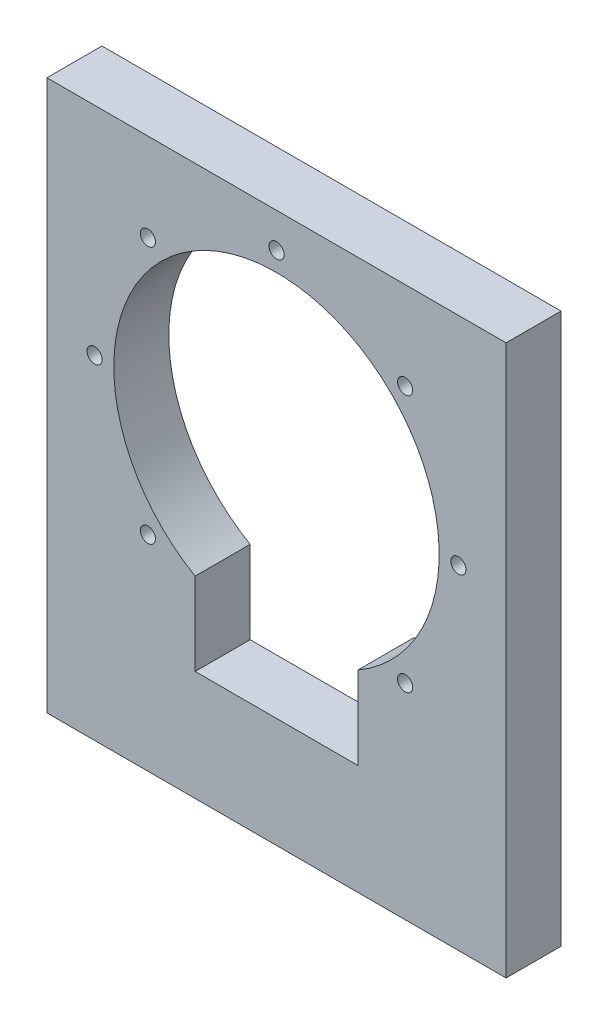
SolidWorks part; units mm, degrees
material "1060 Alloy"
ref_plane "Front Plane" through (0, 0, 0) normal (0, 0, 1) x (1, 0, 0)
ref_plane "Top Plane" through (0, 0, 0) normal (0, 1, 0) x (1, 0, 0)
ref_plane "Right Plane" through (0, 0, 0) normal (1, 0, 0) x (0, 0, -1)
sketch "Sketch1" plane through (0, 0, 0) normal (0, 0, 1) x (1, 0, 0)
  line L1 (0, 76.2) -> (106, 76.2)
  line L5 (0, 76.2) -> (0, -50.8)
  line L6 (0, -50.8) -> (106, -50.8)
  line L7 (0, 76.2) -> (0, -50.8) construction
  line L8 (53, 26.2) -> (53, -11.3) construction
  line L9 (53, 26.2) -> (34.2182, -6.3309) construction
  line L10 (53, 26.2) -> (71.7818, -6.3309) construction
  line L11 (34.2182, -6.3309) -> (34.2182, -25.4)
  line L12 (71.7818, -6.3309) -> (71.7818, -25.4)
  line L13 (71.7818, -25.4) -> (34.2182, -25.4)
  line L21 (106, 76.2) -> (106, -50.8)
  arc A6 (71.7818, -6.3309) -> (34.2182, -6.3309) centre (53, 26.2) ccw
  circle A7 centre (53, 26.2) radius 42 construction
  circle A9 centre (82.6985, 55.8985) radius 1.746
  circle A10 centre (95, 26.2) radius 1.746
  circle A11 centre (82.6985, -3.4985) radius 1.746
  circle A13 centre (23.3015, -3.4985) radius 1.746
  circle A14 centre (11, 26.2) radius 1.746
  circle A15 centre (23.3015, 55.8985) radius 1.746
  circle A33 centre (53, 68.2) radius 1.746
  point P0 (0, 0)
  point P6 (53, 26.2)
  point P32 (53, 26.2)
  point P38 (53, 26.2)
  dimension "D6" = 75.127
  dimension "D7" = 84
  dimension "D8" = 3.492
  dimension "D3" = 3.492
  dimension "D9" = 3.492
  dimension "D4" = 53
  dimension "D5" = 50
  dimension "D10" = 30
  dimension "D11" = 30
  dimension "D2" = 25.4
  dimension "D12" = 127
  dimension "D13" = 106
extrude "Boss-Extrude1" add sketch "Sketch1" along normal blind 12.7
equation "\"bplate_length\"= 24in"
equation "\"bplate_height\"= 6in"
equation "\"bplate_thickness\"= 0.5in"
equation "\"motor_diameter\"= 96 / 25.4in"
equation "\"motor_clearance\"= 5 / 25.4in"
equation "\"motor_mount_hole_pattern_dia\"= 84 / 25.4in"
equation "\"motor_mount_hole_dia\"= 4 / 25.4in"
equation "\"motor_cx\"= \"motor_clearance\" + \"motor_diameter\" / 2in"
equation "\"motor_cy_top\"= \"motor_mount_hole_pattern_dia\" / 2 + \"motor_mount_hole_dia\" * 2in"
equation "\"motor_driver_cover_dia\"= 75 / 25.4in"
equation "\"D4@Sketch1\"=\"motor_cx\""
equation "\"motor_driver_cutout_clearance\"= 60deg"
equation "\"wire_cutout_clearance\"= 2in"
equation "\"connector_plate_thickness\"= 1in"
equation "\"connector_plate_hole_diameter\"= 0.5in"
equation "\"connector_plate_hole_depth\"= 1in"
equation "\"coonector_first_hole_offset\"= 1.6in"
equation "\"D6@Sketch1\"=\"motor_driver_cover_dia\"+0.005"
equation "\"D7@Sketch1\"=\"motor_mount_hole_pattern_dia\""
equation "\"D8@Sketch1\"=\"motor_mount_hole_dia\" - 0.02"
equation "\"D3@Sketch1\"=\"motor_mount_hole_dia\" - 0.02"
